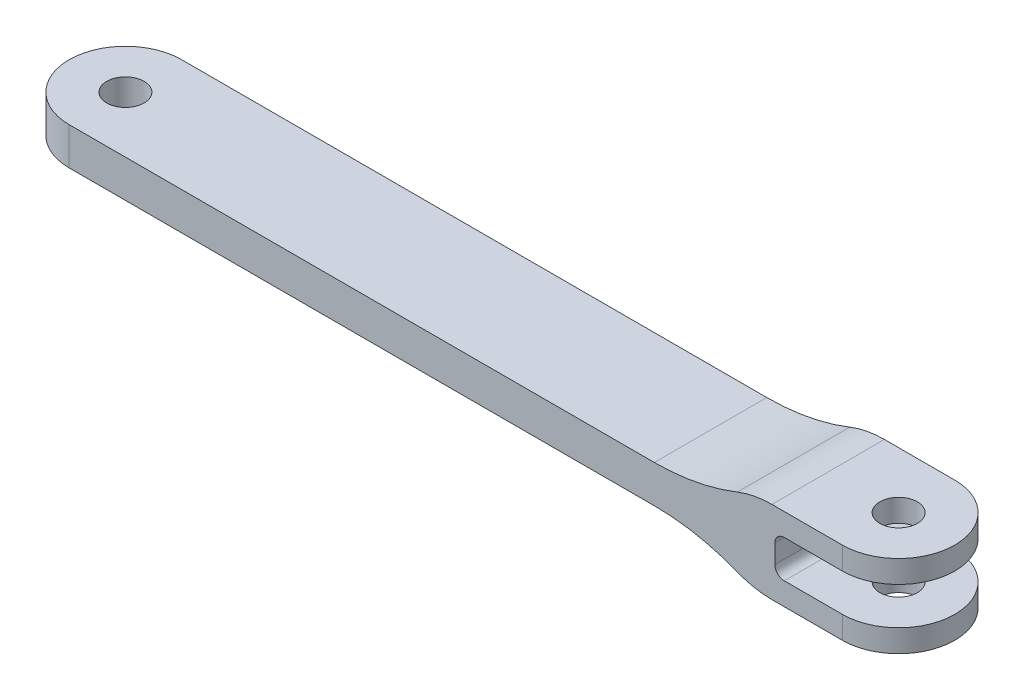
SolidWorks part; units mm, degrees
ref_plane "Front Plane" through (0, 0, 0) normal (0, 0, 1) x (1, 0, 0)
ref_plane "Top Plane" through (0, 0, 0) normal (0, 1, 0) x (1, 0, 0)
ref_plane "Right Plane" through (0, 0, 0) normal (1, 0, 0) x (0, 0, -1)
sketch "Sketch1" plane through (0, 0, 0) normal (0, 1, 0) x (1, 0, 0)
  line L0 (-51.5566, 0) -> (51.5566, 0) construction
  line L1 (-51.5566, 7.5) -> (51.5566, 7.5)
  line L2 (-51.5566, -7.5) -> (51.5566, -7.5)
  arc A0 (-51.5566, 7.5) -> (-51.5566, -7.5) centre (-51.5566, 0) ccw
  arc A1 (51.5566, -7.5) -> (51.5566, 7.5) centre (51.5566, 0) ccw
  circle A2 centre (-51.5566, 0) radius 2.4
  circle A3 centre (51.5566, 0) radius 2.4
  point P3 (0, 0)
  dimension "D1" = 103.1132
  dimension "D2" = 15
extrude "Boss-Extrude1" add sketch "Sketch1" along normal blind 5
sketch "Sketch3" plane through (0, 5, 0) normal (0, 1, 0) x (1, 0, 0)
  line L0 (-51.5566, -7.5) -> (51.5566, -7.5) construction
  line L1 (51.5566, 7.5) -> (39.5566, 7.5)
  line L3 (51.5566, -7.5) -> (39.5566, -7.5)
  line L4 (39.5566, 7.5) -> (39.5566, -7.5)
  circle A0 centre (51.5566, 0) radius 2.4
  arc A1 (51.5566, -7.5) -> (51.5566, 7.5) centre (51.5566, 0) ccw
  dimension "D1" = 12
extrude "Boss-Extrude2" add sketch "Sketch3" along normal blind 3 and the other way blind 8
ref_plane "Plane1" through (0, 2.5, 0) normal (0, 1, 0) x (1, 0, 0)
sketch "Sketch4" plane through (0, 2.5, 0) normal (0, 1, 0) x (1, 0, 0)
  line L9 (42.5566, 7.5) -> (42.5566, -7.5)
  line L12 (39.5566, 7.5) -> (39.5566, -7.5)
  line L13 (39.5566, -7.5) -> (51.5566, -7.5)
  line L14 (51.5566, 7.5) -> (39.5566, 7.5)
  line L16 (42.5566, -7.5) -> (51.5566, -7.5)
  line L17 (51.5566, 7.5) -> (42.5566, 7.5)
  circle A5 centre (51.5566, 0) radius 2.4
  circle A6 centre (51.5566, 0) radius 2.4
  arc A10 (51.5566, -7.5) -> (51.5566, 7.5) centre (51.5566, 0) ccw
  arc A11 (51.5566, -7.5) -> (51.5566, 7.5) centre (51.5566, 0) ccw
  dimension "D3" = 9
  dimension "D1" = 0
  dimension "D2" = 0
extrude "Cut-Extrude1" cut sketch "Sketch4" against normal blind 2.5 and the other way blind 2.5
fillet "Fillet1" radius 30 2 edges at (39.5566, 0, 0) (39.5566, 5, 0)
scale "Scale1" scale about centroid uniform scaling yes scale factor 0.8
sketch "Sketch5" plane through (0, 2.5, 0) normal (0, 1, 0) x (1, 0, 0)
  circle A0 centre (-40.4859, 0) radius 2
  circle A1 centre (42.0046, 0) radius 2
extrude "Cut-Extrude2" cut sketch "Sketch5" against normal through all and the other way through all
fillet "Fillet2" radius 1 2 edges at (34.8046, 0.5, 0) (34.8046, 4.5, 0)
fillet "Fillet3" radius 10 2 edges at (32.4046, -1.9, 0) (32.4046, 6.9, 0)
